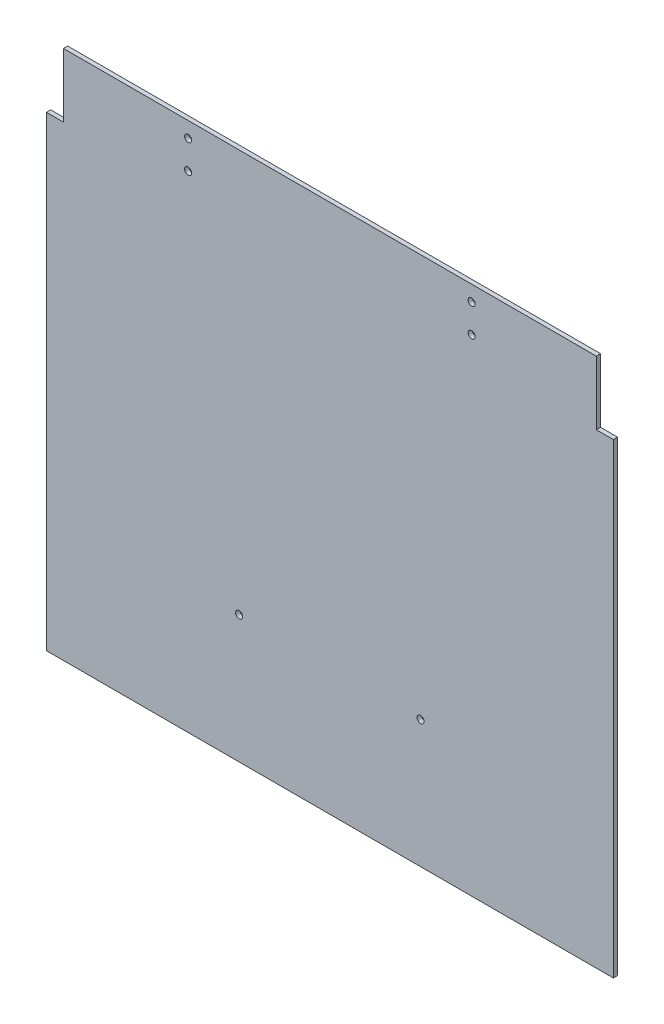
SolidWorks part; units mm, degrees
material "Acrylic (Medium-high impact)"
ref_plane "Front Plane" through (0, 0, 0) normal (0, 0, 1) x (1, 0, 0)
ref_plane "Top Plane" through (0, 0, 0) normal (0, 1, 0) x (1, 0, 0)
ref_plane "Right Plane" through (0, 0, 0) normal (1, 0, 0) x (0, 0, -1)
sketch "Sketch1" plane through (0, 0, 0) normal (0, 0, 1) x (1, 0, 0)
  line L1 (-200, -187) -> (200, -187)
  line L2 (-200, -187) -> (-200, 187)
  line L3 (-200, 187) -> (200, 187)
  line L4 (200, -187) -> (200, 187)
  line L5 (-200, -187) -> (200, 187) construction
  line L6 (-200, 187) -> (200, -187) construction
  point P0 (0, 0)
  dimension "D1" = 400
  dimension "D2" = 374
extrude "Boss-Extrude1" add sketch "Sketch1" along normal blind 3
sketch "Sketch2" plane through (0, 0, 0) normal (0, 0, -1) x (-1, 0, 0)
  line L0 (-200, -187) -> (-200, 187) construction
  line L1 (-200, 187) -> (-188, 187)
  line L2 (-200, 187) -> (-200, 142)
  line L3 (-200, 142) -> (-188, 142)
  line L4 (-1000, 0) -> (49000, 0) construction
  line L5 (-188, 187) -> (-188, 142)
  line L6 (0, -1000) -> (0, 49000) construction
  line L8 (-200, 187) -> (200, 187) construction
  line L10 (-932.2042, 166.06) -> (49067.7958, 166.06) construction
  line L11 (188, 187) -> (188, 142)
  line L12 (200, 142) -> (188, 142)
  line L13 (200, 187) -> (200, 142)
  line L14 (200, 187) -> (188, 187)
  circle A6 centre (-100, 176.06) radius 2.5
  circle A8 centre (-100, 156.06) radius 2.5
  circle A9 centre (100, 156.06) radius 2.5
  circle A10 centre (100, 176.06) radius 2.5
  point P19 (0, 0)
  dimension "D2" = 20.94
  dimension "D3" = 100
  dimension "D5" = 10
  dimension "D6" = 5
  dimension "D1" = 12
  dimension "D4" = 45
extrude "Cut-Extrude1" cut sketch "Sketch2" against normal up to next
sketch "Sketch3" plane through (0, 0, 0) normal (0, 0, -1) x (-1, 0, 0)
  line L0 (0, -1000) -> (0, 49000) construction
  line L1 (-1073.3062, -97) -> (48926.6938, -97) construction
  line L2 (200, -187) -> (-200, -187) construction
  circle A0 centre (64, -97) radius 2.5
  circle A1 centre (-64, -97) radius 2.5
  dimension "D2" = 64
  dimension "D3" = 5
  dimension "D1" = 90
extrude "Cut-Extrude2" cut sketch "Sketch3" against normal up to next
